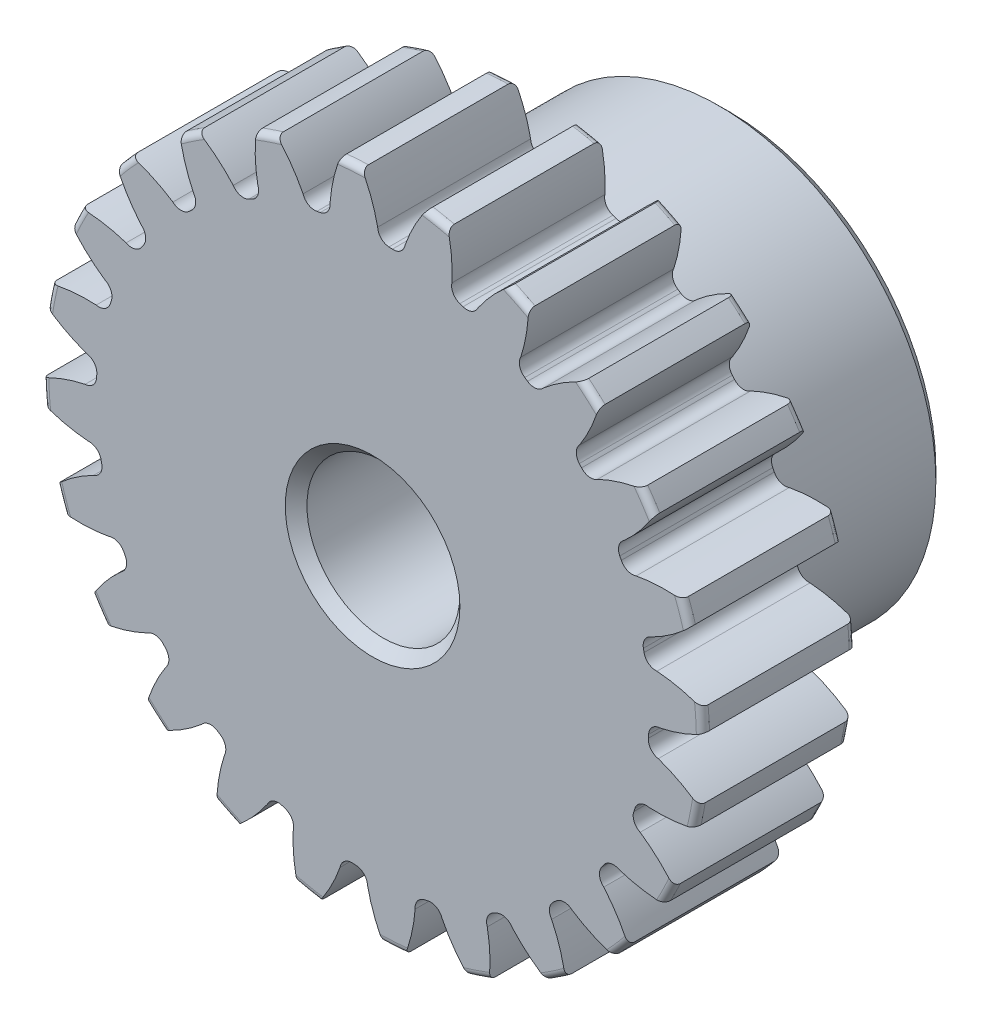
SolidWorks part; units mm, degrees
ref_plane "Front" through (0, 0, 0) normal (0, 0, 1) x (1, 0, 0)
ref_plane "Top" through (0, 0, 0) normal (0, 1, 0) x (1, 0, 0)
ref_plane "Right" through (0, 0, 0) normal (1, 0, 0) x (0, 0, -1)
sketch "Sketch1" plane through (0, 0, 0) normal (0, 0, 1) x (1, 0, 0)
  line L0 (-304.8, 0) -> (304.8, 0) construction
  circle A0 centre (0, 0) radius 10.287
  circle A1 centre (0, 0) radius 9.525 construction
  circle A3 centre (0, 0) radius 8.6066 construction
  dimension "D1" = 0.9184
  dimension "D2" = 1.6804
extrude "Boss-Extrude1" add sketch "Sketch1" against normal blind 4.7625
sketch "Sketch2" plane through (0, 0, 0) normal (1, 0, 0) x (0, 0, -1)
  line L0 (4.7625, 0) -> (11.1252, 0)
  line L1 (4.7625, 0) -> (4.7625, 6.7469)
  line L2 (4.7625, 6.7469) -> (11.1252, 6.7469)
  line L3 (11.1252, 6.7469) -> (11.1252, 0)
  point P5 (11.1252, -6.7469)
  point P6 (0, -10.287)
  point P7 (4.7625, -10.287)
  point P9 (0, 10.287)
revolve "Revolve1" add sketch "Sketch2" angle 360 mid plane about L0
fillet "Fillet2" radius 0.2057 3 edges at (10.287, 0, -4.7625) (10.287, 0, 0) (6.7469, 0, -4.7625)
sketch "Sketch3" plane through (0, 0, 0) normal (0, 0, 1) x (1, 0, 0)
  line L0 (0, 0) -> (0, 10.287) construction
  line L1 (-3.0613, 8.4108) -> (0, 9.525)
  line L2 (-9.5921, 9.525) -> (9.5921, 9.525) construction
  line L3 (-9.0136, 6.2443) -> (9.0136, 12.8057) construction
  line L4 (-3.0613, 8.4108) -> (0, 0) construction
  line L5 (-7.4633, 4.9409) -> (0, 0) construction
  line L6 (-7.4633, 4.9409) -> (-2.5179, 12.411) construction
  line L7 (-2.1265, 8.6943) -> (0, 0) construction
  line L8 (-2.1265, 8.6943) -> (0.0886, 9.2361) construction
  arc A0 (-3.0613, 8.4108) -> (-7.4633, 4.9409) centre (0, 0) ccw
  circle A1 centre (0, 0) radius 9.525 construction
  circle A2 centre (0, 0) radius 8.9506 construction
  arc A3 (-3.0613, 8.4108) -> (-2.1265, 8.6943) centre (0, 0) cw
  circle A4 centre (0, 0) radius 10.287 construction
  point P6 (0, 9.525)
  dimension "D1" = 3.2577
  dimension "D3" = 8.9588
  dimension "D5" = 2.2804
  dimension "D2" = 5.701
  dimension "D4" = 0.9773
sketch "Sketch4" plane through (0, 0, 0) normal (0, 0, 1) x (1, 0, 0)
  line L0 (0, 0) -> (0.6216, 9.4843) construction
  line L1 (0.1581, 8.9492) -> (0.1581, 8.6052)
  line L2 (0, 9.525) -> (1.2433, 9.4435) construction
  line L3 (1.0113, 8.8933) -> (0.9664, 8.5522)
  line L4 (0.1581, 8.6052) -> (0, 0) construction
  line L5 (0, 0) -> (0, 10.287) construction
  line L6 (-7.4633, 4.9409) -> (-2.5179, 12.411) construction
  line L7 (-7.4633, 4.9409) -> (-2.5179, 12.411) construction
  arc A0 (0.9664, 8.5522) -> (0.1581, 8.6052) centre (0, 0) ccw
  arc A1 (0, 9.525) -> (1.2433, 9.4435) centre (0, 0) cw construction
  circle A2 centre (0, 0) radius 9.525 construction
  circle A3 centre (0, 0) radius 8.9506 construction
  circle A4 centre (0, 0) radius 8.6066 construction
  arc A5 (4.1163, 11.9762) -> (-2.5179, 12.411) centre (0, 0) ccw
  spline S0 degree 2 poles (-2.5179, 12.411) (-0.3011, 11.1182) (0.1581, 8.9492) knots 0 0 0 1 1 1
  spline S1 degree 2 poles (4.1163, 11.9762) (1.7498, 10.9838) (1.0113, 8.8933) knots 0 0 0 1 1 1
  dimension "D1" = 1.2468
extrude "Cut-Extrude1" cut sketch "Sketch4" against normal through all
fillet "Fillet1" radius 0.374 2 edges at (0.9664, 8.5522, -2.3813) (0.1581, 8.6052, -2.3813)
pattern_circular "CirPattern1" count 24 over 360 about axis through (0, 0, -4.7625) along (0, 0, 1) of "Cut-Extrude1", "Fillet1"
sketch "Sketch5" plane through (0, 0, 0) normal (0, 0, 1) x (1, 0, 0)
  circle A0 centre (0, 0) radius 2.3813
  circle A1 centre (0, 0) radius 2.3813 construction
  dimension "Bore Min" = 4.7625
  dimension "Bore Max" = 4.7625
extrude "Cut-Extrude2" cut sketch "Sketch5" against normal through all
chamfer "Chamfer1" distance 0.3373 angle 45 3 edges at (6.7469, 0, -11.1252) (2.3813, 0, 0) (2.3813, 0, -11.1252)
sketch "Pitch Dia" plane through (0, 0, 0) normal (0, 0, 1) x (1, 0, 0)
  circle A0 centre (0, 0) radius 9.525 construction
  circle A1 centre (0, 0) radius 9.525 construction
equation "\"D1@Boss-Extrude1\" = \"Face Wd@Sketch2\""
equation "\"D2@Sketch3\" = \"D1@Sketch3\"*1.75"
equation "\"D3@Sketch3\" = \"D1@Sketch3\"+\"D2@Sketch3\""
equation "\"D4@Sketch3\" = \"D1@Sketch3\"*.3"
equation "\"D5@Sketch3\" = \"D1@Sketch3\"-\"D4@Sketch3\""
equation "\"D1@Sketch4\" = 1.5708/(\"Number of Teeth@Sketch1\"/\"Ptich Dia@Sketch1\")"
equation "\"D1@Chamfer1\" = \"B Hub Dia@Sketch2\"*.025"
equation "\"D1@CirPattern1\" = \"Number of Teeth@Sketch1\""
equation "\"D1@Fillet1\" = \"D1@Sketch4\"*.3"
equation "\"D1@Fillet2\" = \"OD@Sketch1\"*.01"
equation "\"D1@Sketch1\" = 1.157/(\"Number of Teeth@Sketch1\"/\"Ptich Dia@Sketch1\")"
